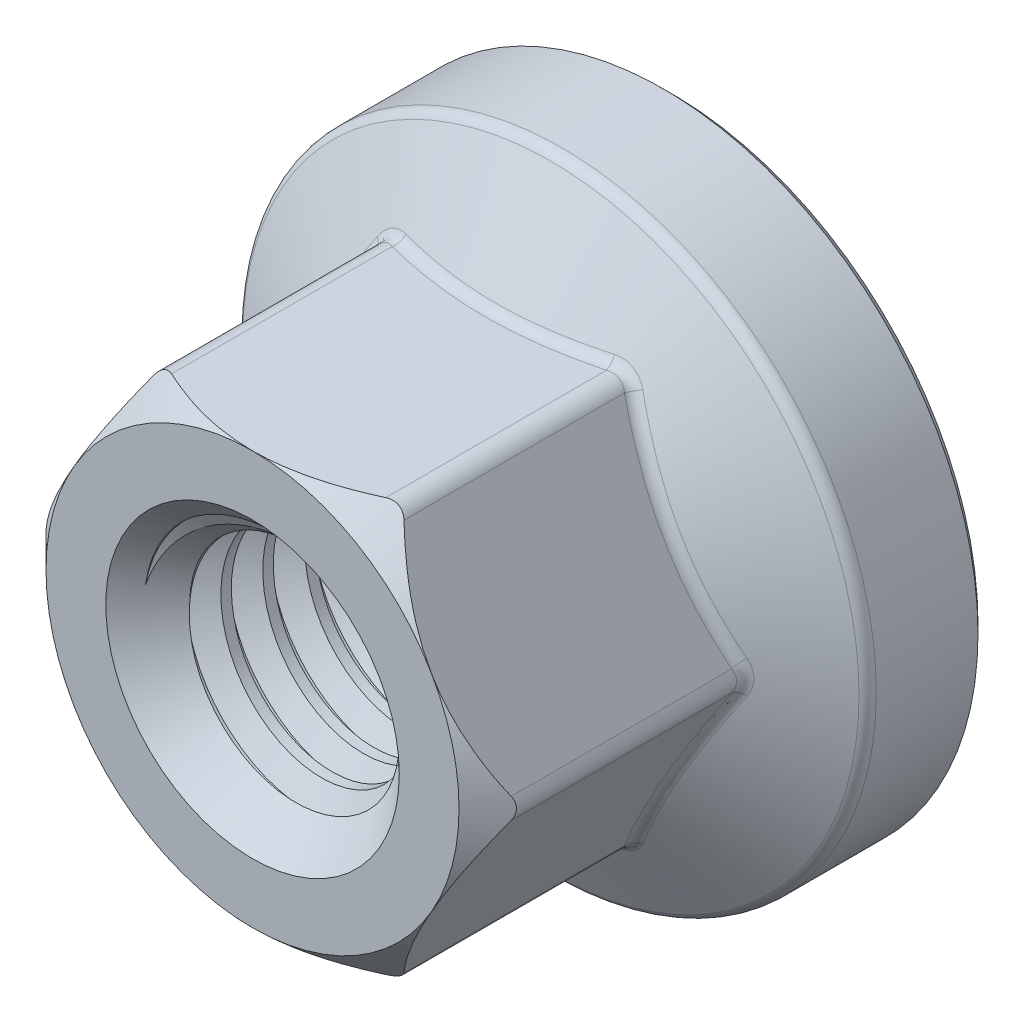
SolidWorks part; units mm, degrees
material "316 Stainless Steel"
ref_plane "Front Plane" through (0, 0, 0) normal (0, 0, 1) x (1, 0, 0)
ref_plane "Top Plane" through (0, 0, 0) normal (0, 1, 0) x (1, 0, 0)
ref_plane "Right Plane" through (0, 0, 0) normal (1, 0, 0) x (0, 0, -1)
ref_axis "CL" through (0, 0, -7.5614) along (0, 0, 1)
sketch "Sketch3" plane through (0, 0, 0) normal (1, 0, 0) x (0, 0, -1)
  line L0 (0, 0) -> (0, 7.5)
  line L1 (0, 7.5) -> (-2.8, 7.5)
  line L2 (-2.8, 7.5) -> (-5.0093, 3.6733)
  line L3 (-5.0093, 3.6733) -> (-5.0093, 0)
  line L4 (-5.0093, 0) -> (0, 0)
  line L5 (0, 0) -> (-13.7555, 0) construction
  line L6 (-4.2867, 4.925) -> (-10, 4.925) construction
  line L7 (-10, 4.925) -> (-10, 0) construction
  dimension "D1" = 60
  dimension "D2" = 15
  dimension "D3" = 10
  dimension "D4" = 2.8
  dimension "D5" = 9.85
revolve "Revolve2" add sketch "Sketch3" angle 360 about L5
ref_plane "Plane2" through (0, 0, 10) normal (0, 0, 1) x (1, 0, 0)
sketch "Sketch4" plane through (0, 0, 10) normal (0, 0, 1) x (1, 0, 0)
  line L1 (2.8435, -4.925) -> (5.6869, 0)
  line L2 (5.6869, 0) -> (2.8435, 4.925)
  line L3 (2.8435, 4.925) -> (-2.8435, 4.925)
  line L4 (-2.8435, 4.925) -> (-5.6869, 0)
  line L5 (-5.6869, 0) -> (-2.8435, -4.925)
  line L6 (-2.8435, -4.925) -> (2.8435, -4.925)
  circle A0 centre (0, 0) radius 4.925 construction
  dimension "D1" = 9.85
extrude "Boss-Extrude1" add sketch "Sketch4" against normal up to next
sketch "Sketch5" plane through (0, 0, 0) normal (1, 0, 0) x (0, 0, -1)
  line L0 (-10, 5.925) -> (-10, 4.925)
  line L1 (-10, 4.925) -> (-9, 5.925)
  line L2 (-9, 5.925) -> (-10, 5.925)
  point P2 (-10, 4.925)
  point P5 (-10, 4.925)
  dimension "D1" = 45
  dimension "D2" = 1
revolve "Cut-Revolve2" cut sketch "Sketch5" angle 360 about axis through (0, 0, -7.5614) along (0, 0, 1)
chamfer "Chamfer5" distance 0.2 angle 45 1 edges at (-7.5, 0, 0)
sketch "Sketch8" plane through (0, 0, 10) normal (0, 0, 1) x (1, 0, 0)
  point P0 (0, 0)
hole_wizard "Tap Drill for M6x1.0 Tap1" positions "Sketch8" profile "Sketch7" hole size "M6x1.0" standard "ANSI Metric" end condition through all
sketch "Sketch7" plane through (0, 0, 10) normal (1, 0, 0) x (0, -1, 0)
  line L0 (0, 0) -> (0, 10)
  line L1 (0, 10) -> (2.5, 10)
  line L2 (2.5, 10) -> (2.5, 0)
  line L5 (2.5, 0) -> (0, 0)
  line L11 (0, -6.35) -> (0, 107.95) construction
  dimension "Thru Hole Dia." = 5
  dimension "Thru Hole Depth" = 10
chamfer "Chamfer3" distance 1 angle 45 1 edges at (2.5, 0, 10)
chamfer "Chamfer4" distance 0.7 angle 45 1 edges at (2.5, 0, 0)
thread "Thread2" pitch 1 start angle 0, offset 1, length 0, pitch 1, diameter 5
ref_plane "Plane3" through (-2.5, 0, 10) normal (0, -1, 0) x (-1, 0, 0)
sketch "Thread Profile2" plane through (-2.5, 0, 10) normal (0, -1, 0) x (-1, 0, 0)
  line L0 (0, 0) -> (0, 1) construction
  line L1 (0, 0) -> (0.5413, 0.3125)
  line L2 (0.5413, 0.3125) -> (0.5413, 0.4375)
  line L3 (0.5413, 0.4375) -> (0, 0.75)
  line L4 (0.5413, 0.375) -> (0, 0.375) construction
  line L11 (0, 0) -> (0, 0.75)
  point P2 (0, 0)
  dimension "Pitch" = 1
  dimension "Profile_Angle" = 60
  dimension "Profile_Land" = 0.125
  dimension "Profile_Height" = 0.5413
fillet "Fillet5" radius 0.5 6 edges at (-5.6869, 0, 6.5424) (-2.8435, -4.925, 6.5424) (5.6869, 0, 6.5424) (2.8435, -4.925, 6.5424) (-2.8435, 4.925, 6.5424) (2.8435, 4.925, 6.5424)
fillet "Fillet6" radius 0.3 13 edges at (-2.7656, 4.8784, 3.8925) (-4.1641, 2.6375, 4.2843) (-5.6076, 0.0441, 3.8925) (-4.3662, -2.2875, 4.2843) (-2.842, -4.8343, 3.8925) (0.1196, -4.925, 4.2858) (2.7656, -4.8784, 3.8925) (4.1641, -2.6375, 4.2843) (5.6076, -0.0441, 3.8925) (4.3662, 2.2875, 4.2843) (2.842, 4.8343, 3.8925) (-0.1196, 4.925, 4.2858) (-7.5, 0, 2.8)
